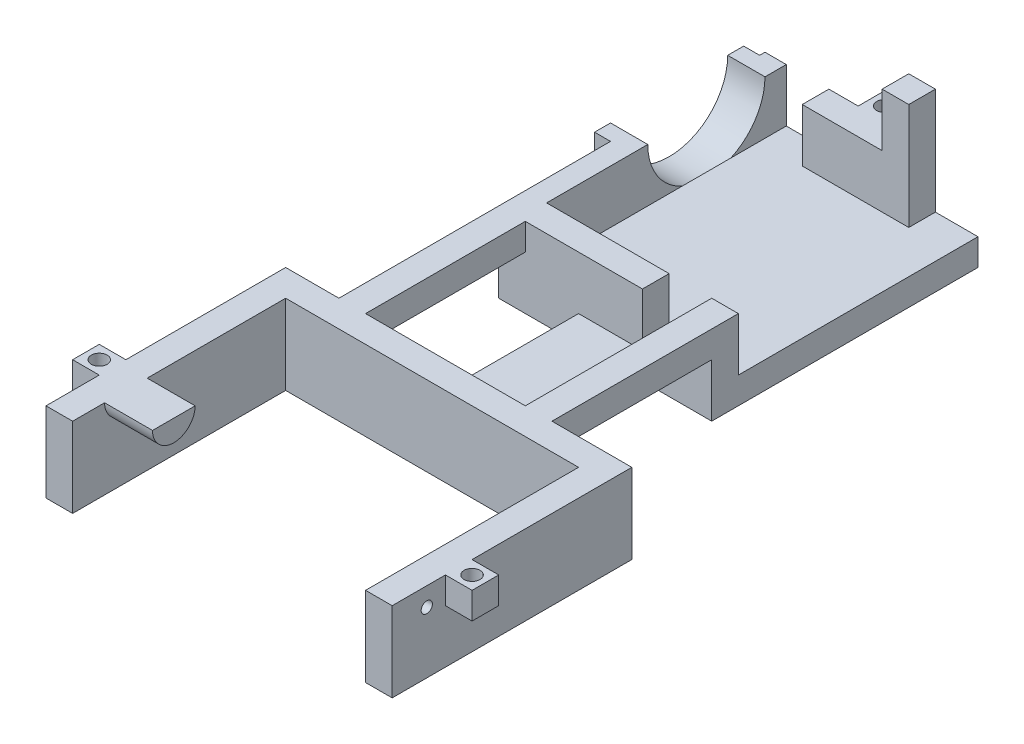
SolidWorks part; units mm, degrees
ref_plane "Front Plane" through (0, 0, 0) normal (0, 0, 1) x (1, 0, 0)
ref_plane "Top Plane" through (0, 0, 0) normal (0, 1, 0) x (1, 0, 0)
ref_plane "Right Plane" through (0, 0, 0) normal (1, 0, 0) x (0, 0, -1)
sketch "Sketch1" plane through (0, 0, 0) normal (0, 1, 0) x (1, 0, 0)
  line L1 (-20, 25) -> (20, 25)
  line L2 (-20, 25) -> (-20, -25)
  line L3 (-20, -25) -> (20, -25)
  line L4 (20, 25) -> (20, -25)
  point P6 (20, 0)
  point P7 (0, 25)
  dimension "D1" = 40
  dimension "D2" = 50
extrude "Boss-Extrude1" add sketch "Sketch1" along normal blind 5
sketch "Sketch3" plane through (0, 5, 0) normal (0, 1, 0) x (1, 0, 0)
  line L0 (20, 25) -> (-20, 25) construction
  line L1 (-8, 25) -> (7, 25)
  line L2 (-8, 25) -> (-8, 20)
  line L3 (-8, 20) -> (7, 20)
  line L4 (7, 25) -> (7, 20)
  line L5 (20, -25) -> (20, 25) construction
  line L6 (-20, -25) -> (20, -25) construction
  line L7 (-20, 25) -> (-16, 25)
  line L10 (-16, 25) -> (-16, -20)
  line L11 (20, -25) -> (15, -25)
  line L12 (20, -25) -> (20, -20)
  line L13 (20, -20) -> (15, -20)
  line L14 (15, -25) -> (15, -20)
  line L15 (7, -25) -> (-20, -25)
  line L16 (7, -25) -> (7, -20)
  line L17 (7, -20) -> (-16, -20)
  line L20 (15, 25) -> (15, 20) construction
  line L21 (15, 20) -> (20, 20) construction
  line L22 (-20, 25) -> (-20, -25)
  line L23 (7, -20) -> (12, -20) construction
  line L24 (12, -20) -> (12, -25) construction
  line L26 (7, 20) -> (12, 20)
  line L27 (7, 20) -> (7, 25)
  line L28 (7, 25) -> (12, 25)
  line L29 (12, 20) -> (12, 25)
  line M17 (-20, 25) -> (-20, -25)
  line M18 (-20, -25) -> (20, -25)
  line M20 (20, 25) -> (-20, 25)
  dimension "D1" = 8
  dimension "D2" = 15
  dimension "D3" = 4
  dimension "D4" = 5
  dimension "D5" = 5
  dimension "D7" = 5
  dimension "D8" = 5
  dimension "D9" = 5
extrude "Boss-Extrude5" add sketch "Sketch3" along normal blind 20 contours L26 L29 L4 M20 region at (9.5, 5, -22.5)
extrude "Boss-Extrude6" add sketch "Sketch3<3>" along normal blind 10 contours L4 L2 L3 M20 | L16 L17 L10 M20 M17 M18 | L12 L11 L14 L13 region at (-0.5, 5, -22.5) region at (-16.5682, 5, -2.5)
sketch "Sketch3<3>" plane through (0, 5, 0) normal (0, 1, 0) x (1, 0, 0) same geometry as "Sketch3"
sketch "Sketch8" plane through (-20, 0, 0) normal (-1, 0, 0) x (0, 0, 1)
  line L0 (-25, 15) -> (25, 15) construction
  line L1 (1, 15) -> (-21, 15)
  arc A0 (-21, 15) -> (1, 15) centre (-10, 15) ccw
  dimension "D1" = 22
extrude "Cut-Extrude3" cut sketch "Sketch8" against normal blind 4
sketch "Sketch10" plane through (-20, 0, 0) normal (-1, 0, 0) x (0, 0, 1)
  line L0 (1, 15) -> (4, 15)
  line L1 (1, 15) -> (25, 15) construction
  line L2 (4, 15) -> (4, 0)
  line L3 (-25, 0) -> (25, 0) construction
  line L4 (4, 0) -> (-24, 0)
  line L5 (-24, 0) -> (-24, 15)
  line L6 (-25, 15) -> (-21, 15) construction
  line L7 (-24, 15) -> (-21, 15)
  arc A0 (-21, 15) -> (1, 15) centre (-10, 15) ccw
  dimension "D1" = 3
extrude "Boss-Extrude9" add sketch "Sketch10" along normal blind 3
sketch "Sketch11" plane through (0, 0, -25) normal (0, 0, -1) x (-1, 0, 0)
  line L0 (-7, 15) -> (8, 15) construction
  line L1 (2.5, 10) -> (-2.5, 10)
  line L2 (2.5, 10) -> (2.5, 15)
  line L3 (2.5, 15) -> (-2.5, 15)
  line L4 (-2.5, 10) -> (-2.5, 15)
  point P6 (0, 10)
  dimension "D1" = 5
  dimension "D2" = 5
extrude "Boss-Extrude10" add sketch "Sketch11" along normal blind 5
sketch "Sketch12" plane through (0, 10, 0) normal (0, -1, 0) x (1, 0, 0)
  line L0 (-2.5, -30) -> (-2.5, -25) construction
  line L1 (20, -25) -> (-20, -25) construction
  circle A0 centre (0, -27.5) radius 1.5
  point P5 (-2.5, -27.5)
  point P8 (0, -25)
  dimension "D1" = 3
extrude "Cut-Extrude4" cut sketch "Sketch12" against normal blind 5
sketch "Sketch14" plane through (0, 0, 25) normal (0, 0, 1) x (1, 0, 0)
  line L0 (15, 15) -> (15, 5) construction
  line L1 (20, 15) -> (15, 15)
  line L2 (20, 15) -> (20, 10)
  line L3 (20, 10) -> (15, 10)
  line L4 (15, 15) -> (15, 10)
  line L5 (-20, 0) -> (20, 0) construction
  line L6 (-20, 15) -> (-15, 15)
  line L7 (-20, 15) -> (-20, 10)
  line L8 (-20, 10) -> (-15, 10)
  line L9 (-15, 15) -> (-15, 10)
  line L10 (-5, 0) -> (5, 0)
  line L11 (-5, 0) -> (-5, 5)
  line L12 (-5, 5) -> (5, 5)
  line L13 (5, 0) -> (5, 5)
  point P18 (0, 5)
  dimension "D1" = 5
  dimension "D2" = 5
  dimension "D3" = 10
extrude "Boss-Extrude12" add sketch "Sketch14" along normal blind 30
sketch "Sketch15" plane through (0, 0, 55) normal (0, 0, 1) x (1, 0, 0)
  line L0 (-5, 0) -> (5, 0) construction
  line L1 (20, 0) -> (-20, 0)
  line L2 (20, 0) -> (20, 15)
  line L3 (20, 15) -> (-20, 15)
  line L4 (-20, 0) -> (-20, 15)
extrude "Boss-Extrude13" add sketch "Sketch15" along normal blind 5
sketch "Sketch16" plane through (20, 0, 0) normal (1, 0, 0) x (0, 0, -1)
  line L1 (-55, 0) -> (-60, 0)
  line L2 (-55, 0) -> (-55, 15)
  line L3 (-55, 15) -> (-60, 15)
  line L4 (-60, 0) -> (-60, 15)
  line M13 (-20, 15) -> (-60, 15)
  line M14 (-60, 15) -> (-60, 0)
  line M15 (-60, 0) -> (-55, 0)
  line M16 (-55, 0) -> (-55, 10)
extrude "Boss-Extrude15" add sketch "Sketch16" along normal blind 15 contours L2 M16 M13 M14 M15 region at (20, 7.5, 57.5)
sketch "Sketch17" plane through (-20, 0, 0) normal (-1, 0, 0) x (0, 0, 1)
  line L0 (4, 15) -> (60, 15) construction
  line L1 (60, 0) -> (55, 0)
  line L2 (60, 0) -> (60, 15)
  line L3 (60, 15) -> (55, 15)
  line L4 (55, 0) -> (55, 15)
  line L5 (55, 10) -> (55, 0) construction
  line M13 (55, 10) -> (55, 0)
  line M14 (55, 0) -> (60, 0)
  line M15 (60, 0) -> (60, 15)
  line M16 (60, 15) -> (4, 15)
extrude "Boss-Extrude17" add sketch "Sketch17" along normal blind 10 contours L4 M13 M14 M15 M16 region at (-20, 7.5, 57.5)
sketch "Sketch18" plane through (0, 0, 60) normal (0, 0, 1) x (1, 0, 0)
  line L0 (35, 15) -> (-30, 15) construction
  line L1 (35, 0) -> (30, 0)
  line L2 (35, 0) -> (35, 15)
  line L3 (35, 15) -> (30, 15)
  line L4 (30, 0) -> (30, 15)
  line L6 (-30, 0) -> (-25, 0)
  line L7 (-30, 0) -> (-30, 15)
  line L8 (-30, 15) -> (-25, 15)
  line L9 (-25, 0) -> (-25, 15)
  dimension "D1" = 5
extrude "Boss-Extrude18" add sketch "Sketch18" along normal blind 40
sketch "Sketch19" plane through (-25, 0, 0) normal (1, 0, 0) x (0, 0, -1)
  line L0 (-55, 15) -> (-100, 15) construction
  line L1 (-86, 15) -> (-94, 15)
  arc A0 (-94, 15) -> (-86, 15) centre (-90, 15) ccw
  dimension "D1" = 8
  dimension "D2" = 10
extrude "Boss-Extrude19" add sketch "Sketch19" along normal blind 9
sketch "Sketch20" plane through (-30, 0, 0) normal (-1, 0, 0) x (0, 0, 1)
  line L0 (100, 15) -> (55, 15) construction
  line L1 (85, 15) -> (90, 15)
  line L2 (85, 15) -> (85, 10)
  line L3 (85, 10) -> (90, 10)
  line L4 (90, 15) -> (90, 10)
  line L5 (100, 15) -> (100, 0) construction
  dimension "D1" = 5
  dimension "D2" = 5
  dimension "D3" = 10
extrude "Boss-Extrude20" add sketch "Sketch20" along normal blind 5
sketch "Sketch21" plane through (0, 10, 0) normal (0, -1, 0) x (1, 0, 0)
  line L0 (-35, 85) -> (-35, 90) construction
  line L1 (-35, 85) -> (-30, 85) construction
  circle A0 centre (-32.5, 87.5) radius 1.5
  point P4 (-35, 87.5)
  point P7 (-32.5, 85)
  dimension "D1" = 3
extrude "Cut-Extrude5" cut sketch "Sketch21" against normal blind 5
sketch "Sketch22" plane through (35, 0, 0) normal (1, 0, 0) x (0, 0, -1)
  line L1 (-85, 10) -> (-90, 10)
  line L2 (-85, 10) -> (-85, 15)
  line L3 (-85, 15) -> (-90, 15)
  line L4 (-90, 10) -> (-90, 15)
  line L5 (-55, 15) -> (-100, 15) construction
  line L6 (-100, 0) -> (-100, 15) construction
  dimension "D1" = 5
  dimension "D2" = 5
  dimension "D3" = 10
extrude "Boss-Extrude21" add sketch "Sketch22" along normal blind 5
sketch "Sketch23" plane through (0, 10, 0) normal (0, -1, 0) x (1, 0, 0)
  line L0 (40, 90) -> (40, 85) construction
  line L1 (40, 90) -> (35, 90) construction
  circle A0 centre (37.5, 87.5) radius 1.5
  point P4 (40, 87.5)
  point P8 (37.5, 90)
  dimension "D1" = 3
extrude "Cut-Extrude6" cut sketch "Sketch23" against normal blind 5
sketch "Sketch24" plane through (30, 0, 0) normal (-1, 0, 0) x (0, 0, 1)
  line L0 (90, 15) -> (97, 15) construction
  line L1 (100, 15) -> (60, 15) construction
  line L2 (90, 15) -> (83, 15) construction
  line L3 (90, 15) -> (90, 8) construction
  line L4 (83, 15) -> (90, 8) construction
  line L5 (90, 8) -> (97, 15) construction
  circle A0 centre (93.5, 11.5) radius 1.05
  circle A1 centre (86.5, 11.5) radius 1.05
  point P0 (93.5, 11.5)
  point P8 (86.5, 11.5)
  dimension "D7" = 2.1
  dimension "D1" = 7
  dimension "D2" = 7
  dimension "D3" = 7
  dimension "D8" = 3
extrude "Cut-Extrude7" cut sketch "Sketch24" against normal blind 5
